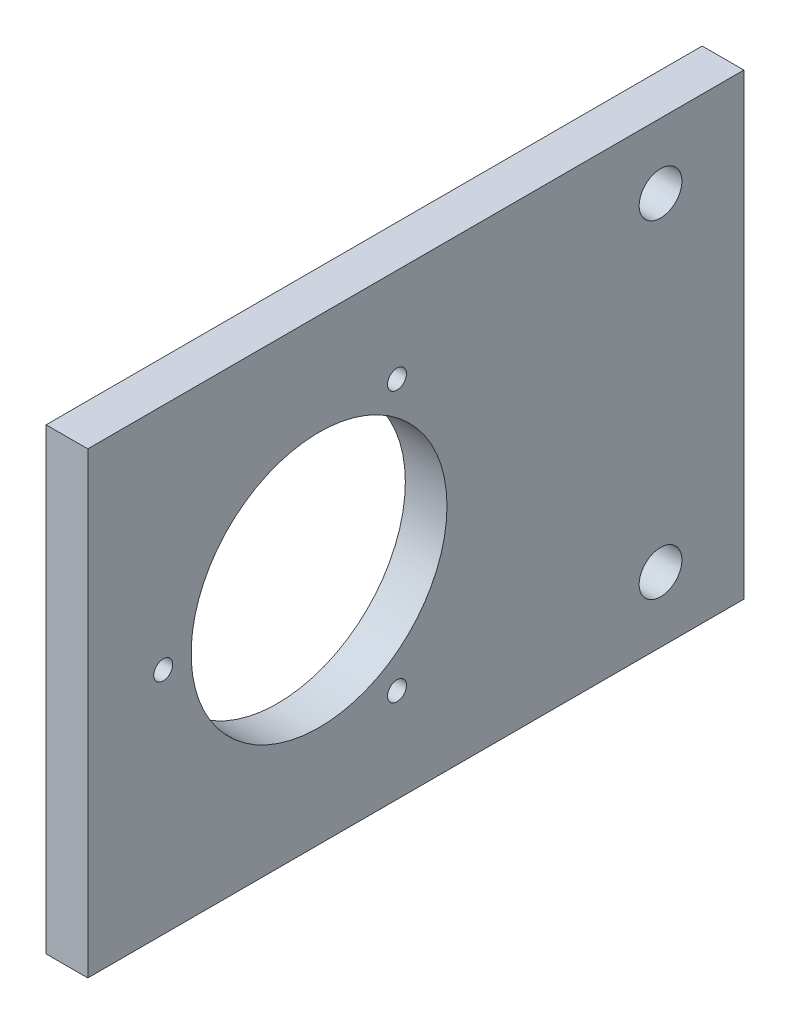
SolidWorks part; units mm, degrees
ref_plane "Front Plane" through (0, 0, 0) normal (1, 0, 0) x (0, 1, 0)
ref_plane "Top Plane" through (0, 0, 0) normal (0, 0, 1) x (0, 1, 0)
ref_plane "Right Plane" through (0, 0, 0) normal (0, 1, 0) x (-1, 0, 0)
sketch "Sketch1" plane through (0, 0, 0) normal (1, 0, 0) x (0, 1, 0)
  line L0 (0, 50) -> (0, -50) construction
  line L1 (-34.925, -50) -> (34.925, -50)
  line L2 (-34.925, -50) -> (-34.925, 50)
  line L3 (-34.925, 50) -> (34.925, 50)
  line L4 (34.925, -50) -> (34.925, 50)
  line L5 (-34.925, -50) -> (34.925, 50) construction
  line L6 (-34.925, 50) -> (34.925, -50) construction
  line L7 (-34.925, 14.75) -> (34.925, 14.75) construction
  line L8 (0, 14.75) -> (0, 38.5) construction
  line L9 (-25, -37.3) -> (25, -37.3) construction
  line L10 (-25, -37.3) -> (-25, 37.3) construction
  line L11 (-25, 37.3) -> (25, 37.3) construction
  line L12 (25, -37.3) -> (25, 37.3) construction
  line L13 (-25, -37.3) -> (25, 37.3) construction
  line L14 (-25, 37.3) -> (25, -37.3) construction
  line L15 (0, 14.75) -> (-20.5681, 2.875) construction
  line L16 (0, 14.75) -> (20.5681, 2.875) construction
  circle A5 centre (0, 14.75) radius 19.5
  circle A6 centre (-25, -37.3) radius 3.2576
  circle A7 centre (25, -37.3) radius 3.2576
  circle A8 centre (0, 38.5) radius 1.45
  circle A9 centre (20.5681, 2.875) radius 1.45
  circle A10 centre (-20.5681, 2.875) radius 1.45
  point P0 (0, 0)
  point P20 (0, 0)
  dimension "D5" = 120
  dimension "D6" = 2.9
  dimension "D7" = 23.75
  dimension "D8" = 39
  dimension "D11" = 23.75
  dimension "D12" = 6.5151
  dimension "D4" = 120
  dimension "D1" = 69.85
  dimension "D2" = 100
  dimension "D3" = 64.75
  dimension "D9" = 12.7
  dimension "D10" = 50
extrude "Boss-Extrude1" add sketch "Sketch1" along normal blind 6.35
